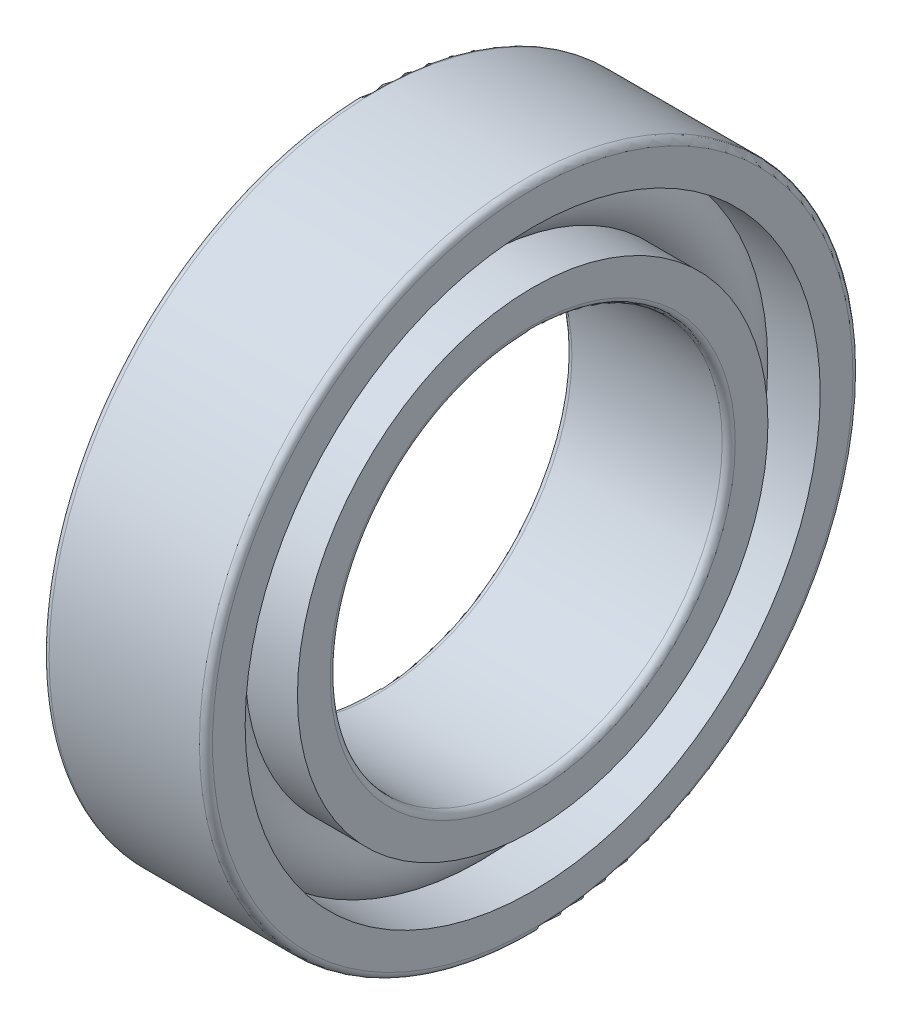
SolidWorks part; units mm, degrees
ref_plane "Plane1" through (0, 0, 0) normal (0, 0, 1) x (1, 0, 0)
ref_plane "Plane2" through (0, 0, 0) normal (0, 1, 0) x (1, 0, 0)
ref_plane "Plane3" through (0, 0, 0) normal (1, 0, 0) x (0, 0, -1)
sketch "Clipboard" plane through (0, 0, 0) normal (0, 0, 1) x (1, 0, 0)
  line L0 (-10, 0) -> (10, 0) construction
  line L1 (0, 0) -> (22.3471, -0.7804)
  line L2 (0, 0) -> (3.9976, 0.1396)
  line L3 (0, 0) -> (22.3471, -0.7804)
  line L4 (0, 0) -> (-22.3573, -0.3902)
  dimension "BallCLRad" = 4
sketch "CagSpiSke" plane through (0, 0, 0) normal (0, 0, 1) x (1, 0, 0)
  line L0 (0.06, 3.9) -> (0.06, 4.1)
  line L1 (0.06, 4.1) -> (-0.06, 4.1)
  line L2 (-0.06, 4.1) -> (-0.06, 3.9)
  line L3 (-0.06, 3.9) -> (0.06, 3.9)
  line L4 (-20.6375, 0) -> (20.6375, 0) construction
  line L5 (0, 0) -> (0, 23.7692) construction
  dimension "OD" = 8.2
  dimension "ID" = 7.8
revolve "CageSpine" add sketch "CagSpiSke" angle 0.001 about L4 reverse direction yes
ref_axis "Axis1" through (-50, 0, 0) along (1, 0, 0)
sketch "CagBalSke" plane through (0, 0, 0) normal (0, 0, 1) x (1, 0, 0)
  line L0 (-0.66, 4) -> (0.66, 4)
  line L1 (-1.905, 4) -> (1.905, 4) construction
  line L2 (-10, 0) -> (10, 0) construction
  line L3 (0, 0) -> (0, 24) construction
  arc A0 (0.66, 4) -> (-0.66, 4) centre (0, 4) cw
  dimension "BallCLRad" = 4
revolve "CageBall" [suppressed] add sketch "CagBalSke" angle 360 about L1 reverse direction yes
pattern_circular "CageBalls" [suppressed] count 2 every 180 about axis through (-50, 0, 0) along (1, 0, 0)
sketch "CagTrmODSke" plane through (0, 0, 0) normal (0, 0, 1) x (1, 0, 0)
  line L0 (0.661, 4.1) -> (0.661, 4.661)
  line L1 (0.661, 4.661) -> (-0.661, 4.661)
  line L2 (-0.661, 4.661) -> (-0.661, 4.1)
  line L3 (-0.661, 4.1) -> (0.661, 4.1)
  line L4 (-20.6375, 0) -> (20.6375, 0) construction
  line L5 (0, 0) -> (0, 25) construction
  dimension "Width" = 1.322
  dimension "ID" = 8.2
  dimension "OD" = 9.322
revolve "CageTrimOD" [suppressed] cut sketch "CagTrmODSke" angle 360 about L4 reverse direction yes
sketch "CagTrmIDSke" plane through (0, 0, 0) normal (0, 0, 1) x (1, 0, 0)
  line L0 (0.661, 3.341) -> (0.661, 3.9)
  line L1 (0.661, 3.9) -> (-0.661, 3.9)
  line L2 (-0.661, 3.9) -> (-0.661, 3.341)
  line L3 (-0.661, 3.341) -> (0.661, 3.341)
  line L4 (-20.6375, 0) -> (20.6375, 0) construction
  line L5 (0, 0) -> (0, 25) construction
  dimension "Width" = 1.322
  dimension "ID" = 6.682
  dimension "OD" = 7.8
revolve "CageTrimID" [suppressed] cut sketch "CagTrmIDSke" angle 360 about L4 reverse direction yes
sketch "BalSimSke" plane through (0, 0, 0) normal (0, 0, 1) x (1, 0, 0)
  line L0 (-10, 0) -> (10, 0) construction
  line L1 (-10, 4) -> (10, 4) construction
  line L2 (0, 0) -> (0, 23) construction
  circle A0 centre (0, 4) radius 0.6
  dimension "BallCLRad" = 4
  dimension "Ball_diameter" = 1.2
revolve "BallsSimplified" add sketch "BalSimSke" angle 360 about L0
sketch "BalDetSke" plane through (0, 0, 0) normal (0, 0, 1) x (1, 0, 0)
  line L0 (-0.6, 4) -> (0.6, 4)
  line L1 (-1.905, 4) -> (1.905, 4) construction
  line L2 (0, 0) -> (0, 25) construction
  arc A0 (0.6, 4) -> (-0.6, 4) centre (0, 4) cw
  dimension "BallCLRad" = 4
  dimension "Ball_diameter" = 1.2
revolve "BallDetailed" [suppressed] add sketch "BalDetSke" angle 360 about L1 reverse direction yes
sketch "InnRacSke" plane through (0, 0, 0) normal (0, 0, 1) x (1, 0, 0)
  line L0 (-0.4131, 3.6) -> (-1.25, 3.6)
  line L1 (-1.25, 3.6) -> (-1.25, 3.1)
  line L2 (-1.15, 3) -> (1.15, 3)
  line L3 (1.25, 3.1) -> (1.25, 3.6)
  line L4 (1.25, 3.6) -> (0.4131, 3.6)
  line L5 (-20.6375, 0) -> (20.6375, 0) construction
  line L6 (0, 0) -> (0, 30) construction
  arc A0 (-1.25, 3.1) -> (-1.15, 3) centre (-1.15, 3.1) ccw
  arc A1 (1.15, 3) -> (1.25, 3.1) centre (1.15, 3.1) ccw
  arc A2 (0.4131, 3.6) -> (-0.4131, 3.6) centre (0, 4) cw
  dimension "BallCLRad" = 4
  dimension "Fillet_radius" = 0.1
  dimension "Ball_diameter" = 1.15
  dimension "ID" = 6
  dimension "OD" = 7.2
  dimension "Width" = 2.5
revolve "InnerRace" add sketch "InnRacSke" angle 360 about L5 reverse direction yes
sketch "OutRacSke" plane through (0, 0, 0) normal (0, 0, 1) x (1, 0, 0)
  line L0 (-0.4131, 4.4) -> (-1.25, 4.4)
  line L1 (-1.25, 4.4) -> (-1.25, 4.9)
  line L2 (-1.15, 5) -> (1.15, 5)
  line L3 (1.25, 4.9) -> (1.25, 4.4)
  line L4 (1.25, 4.4) -> (0.4131, 4.4)
  line L5 (-20.6375, 0) -> (20.6375, 0) construction
  line L6 (0, 0) -> (0, 30) construction
  arc A0 (-1.25, 4.9) -> (-1.15, 5) centre (-1.15, 4.9) cw
  arc A1 (1.15, 5) -> (1.25, 4.9) centre (1.15, 4.9) cw
  arc A2 (0.4131, 4.4) -> (-0.4131, 4.4) centre (0, 4) ccw
  dimension "BallCLRad" = 4
  dimension "Fillet_radius" = 0.1
  dimension "Ball_diameter" = 1.15
  dimension "Width" = 2.5
revolve "OuterRace" add sketch "OutRacSke" angle 360 about L5 reverse direction yes
pattern_circular "BallsDetailed" [suppressed] count 2 every 180 about axis through (-50, 0, 0) along (1, 0, 0)
equation "\"BallCLRad@Clipboard\" = ( \"OD@OutRacSke\" + \"ID@InnRacSke\" ) / 4"
equation "\"BallCLRad@BalSimSke\" = \"BallCLRad@Clipboard\""
equation "\"BallCLRad@BalDetSke\" = \"BallCLRad@Clipboard\""
equation "\"BallCLRad@InnRacSke\" = \"BallCLRad@Clipboard\""
equation "\"BallCLRad@OutRacSke\" = \"BallCLRad@Clipboard\""
equation "\"Ball_diameter@InnRacSke\" = \"Ball_diameter@BalDetSke\" - 0.05"
equation "\"Ball_diameter@OutRacSke\" = \"Ball_diameter@BalDetSke\" - 0.05"
equation "\"Ball_diameter@BalSimSke\" = \"Ball_diameter@BalDetSke\""
equation "\"Width@OutRacSke\" = \"Width@InnRacSke\""
equation "\"Fillet_radius@OutRacSke\" = \"Fillet_radius@InnRacSke\""
equation "\"Max_count@Clipboard\" = int( 3.14159265 / atn(( \"Ball_diameter@BalDetSke\" / 2) / sqr( \"BallCLRad@Clipboard\"  *  \"BallCLRad@Clipboard\" - ( \"Ball_diameter@BalDetSke\" / 2) *  ( \"Ball_diameter@BalDetSke\" / 2))))"
equation "\"Max_count@Clipboard\" = ((sgn( \"Max_count@Clipboard\" - \"Count@Clipboard\" )-1)*( \"Max_count@Clipboard\" - \"Count@Clipboard\" ))/-2+ \"Count@Clipboard\""
equation "\"Count@BallsDetailed\" = int( \"Show_count@Clipboard\" ) "
equation "\"Count@BallsDetailed\" = ((sgn( \"Count@BallsDetailed\" - \"Max_count@Clipboard\" )-1)*( \"Count@BallsDetailed\" - \"Max_count@Clipboard\" ))/-2+ \"Max_count@Clipboard\""
equation "\"Count@BallsDetailed\" = ((sgn( \"Count@BallsDetailed\" - \"Min_count@Clipboard\" )+1)*( \"Count@BallsDetailed\" - \"Min_count@Clipboard\"))/2 +\"Min_count@Clipboard\""
equation "\"Angle@BallsDetailed\" = 360.0 / \"Max_count@Clipboard\""
equation "\"BallCLRad@CagBalSke\" = \"BallCLRad@Clipboard\""
equation "\"Count@CageBalls\" = \"Count@BallsDetailed\""
equation "\"Angle@CageBalls\" = \"Angle@BallsDetailed\""
equation "\"Angle@CageSpine\" =  \"Angle@CageBalls\" * ( \"Count@CageBalls\" -1 + int( \"Count@CageBalls\" / \"Max_count@Clipboard\" ) )  + 0.001 -  int( \"Count@CageBalls\" / \"Max_count@Clipboard\" ) * 0.001"
equation "\"Angle@CageSpine\" =  \"Angle@CageSpine\" * int( \"Min_count@Clipboard\" / 2) + int(1 / \"Min_count@Clipboard\")  * 0.001"
equation "\"CageWallOD@CagBalSke\" =  \"Ball_diameter@BalDetSke\" * 1.1"
equation "\"Thickness@CagSpiSke\" =  \"Ball_diameter@BalDetSke\" * 0.1"
equation "\"OD@CagTrmODSke\" = \"BallCLRad@Clipboard\" * 2 + \"CageWallOD@CagBalSke\" + 0.002"
equation "\"ID@CagTrmODSke\" = \"BallCLRad@Clipboard\" * 2 + \"Ball_diameter@BalDetSke\" / 6"
equation "\"OD@CagTrmIDSke\" = \"BallCLRad@Clipboard\" * 2 - \"Ball_diameter@BalDetSke\" / 6"
equation "\"ID@CagTrmIDSke\" = \"BallCLRad@Clipboard\" * 2 - \"CageWallOD@CagBalSke\" + 0.002"
equation "\"OD@CagSpiSke\" = \"ID@CagTrmODSke\""
equation "\"ID@CagSpiSke\" = \"OD@CagTrmIDSke\""
equation "\"Width@CagTrmODSke\" = \"CageWallOD@CagBalSke\" + 0.002"
equation "\"Width@CagTrmIDSke\" = \"CageWallOD@CagBalSke\" + 0.002"
